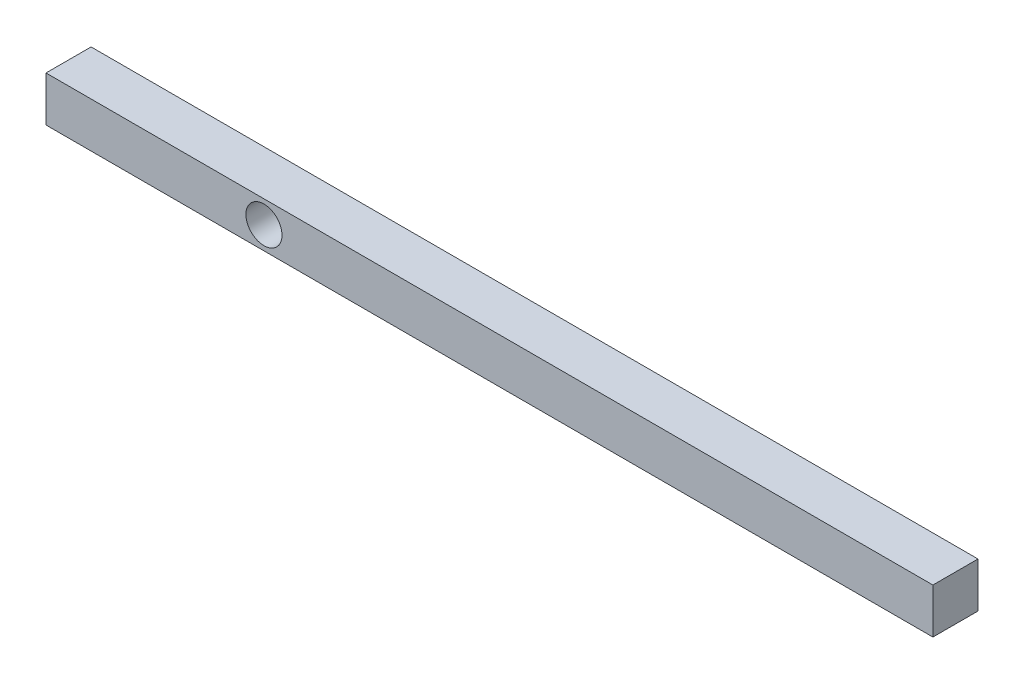
SolidWorks part; units mm, degrees
material "Plain Carbon Steel"
ref_plane "Front Plane" through (0, 0, 0) normal (0, 0, 1) x (1, 0, 0)
ref_plane "Top Plane" through (0, 0, 0) normal (0, 1, 0) x (1, 0, 0)
ref_plane "Right Plane" through (0, 0, 0) normal (1, 0, 0) x (0, 0, -1)
sketch "Sketch1" plane through (0, 0, 0) normal (0, 0, 1) x (1, 0, 0)
  line L0 (-58, -6) -> (178, -6)
  line L1 (178, -6) -> (178, 6)
  line L2 (178, 6) -> (-58, 6)
  line L3 (-58, 6) -> (-58, -6)
extrude "Boss-Extrude1" add sketch "Sketch1" along normal mid plane 12
sketch "Sketch2" plane through (0, 0, 0) normal (0, 0, 1) x (1, 0, 0)
  circle A0 centre (0, 0) radius 4.8
  dimension "D1" = 9.6
extrude "Cut-Extrude1" cut sketch "Sketch2" against normal mid plane 24
